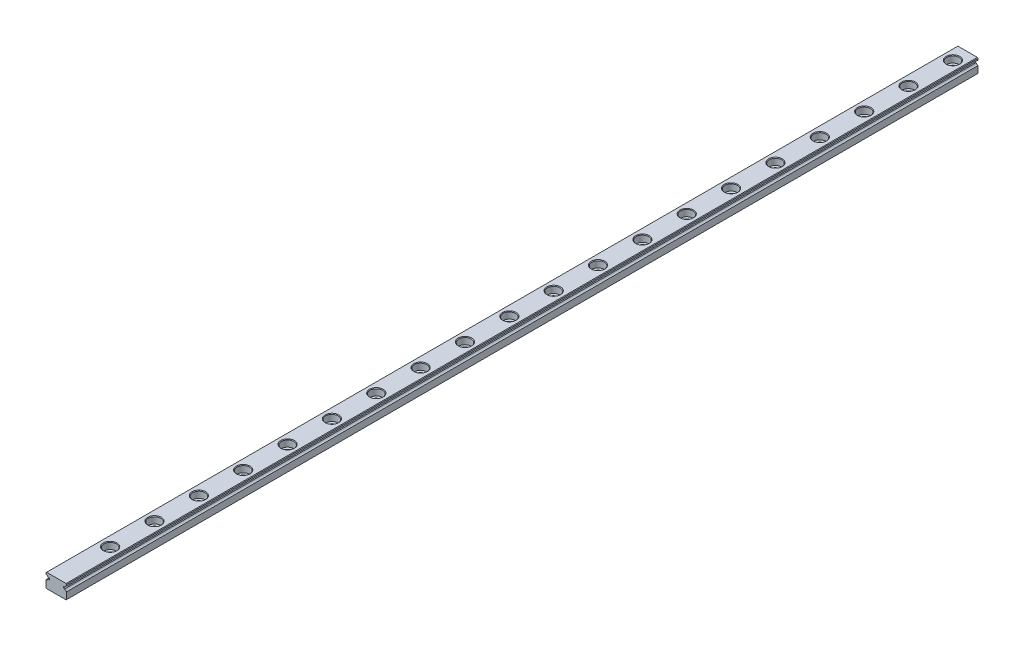
SolidWorks part; units mm, degrees
material "AISI 1020"
ref_plane "Спереди" through (0, 0, 0) normal (0, 0, 1) x (1, 0, 0)
ref_plane "Сверху" through (0, 0, 0) normal (0, 1, 0) x (1, 0, 0)
ref_plane "Справа" through (0, 0, 0) normal (1, 0, 0) x (0, 0, -1)
sketch "Sketch1" plane through (0, 0, 0) normal (0, 0, 1) x (1, 0, 0)
  line L0 (0, 0) -> (0, 4.3706) construction
  line L1 (-3.3, -2.4) -> (3.3, -2.4)
  line L2 (-3.5, -2.2) -> (-3.5, 0.1063)
  line L3 (-3.3, 2.4) -> (3.3, 2.4)
  line L4 (3.5, -2.2) -> (3.5, 0.1063)
  line L5 (-3.5, -2.4) -> (3.5, 2.4) construction
  line L6 (-3.5, 2.4) -> (3.5, -2.4) construction
  line L7 (-3.5, 1.6937) -> (-3.5, 2.2)
  line L8 (3.5, 1.6937) -> (3.5, 2.2)
  line L9 (-3.5, -2.2) -> (-3.3, -2.4)
  line L10 (3.3, -2.4) -> (3.5, -2.2)
  line L11 (3.3, 2.4) -> (3.5, 2.2)
  line L12 (-3.5, 2.2) -> (-3.3, 2.4)
  line L13 (2.8401, 0.65) -> (2.3401, 0.65)
  line L14 (-2.8401, 0.65) -> (-2.3401, 0.65)
  line L15 (2.3401, 0.65) -> (2.3401, 1.15)
  line L16 (-2.8401, 1.15) -> (-2.3401, 1.15)
  line L17 (-2.3401, 0.65) -> (-2.3401, 1.15)
  line L18 (2.8401, 1.15) -> (2.3401, 1.15)
  arc A0 (-3.5, 1.6937) -> (-2.8401, 1.15) centre (-3.6, 0.9) cw
  arc A1 (3.5, 1.6937) -> (2.8401, 1.15) centre (3.6, 0.9) ccw
  arc A2 (-2.8401, 0.65) -> (-3.5, 0.1063) centre (-3.6, 0.9) cw
  arc A3 (2.8401, 0.65) -> (3.5, 0.1063) centre (3.6, 0.9) ccw
  point P0 (0, 0)
  dimension "D4" = 0.8
  dimension "D5" = 0.1
  dimension "D1" = 7
  dimension "D2" = 4.8
  dimension "D3" = 1.5
  dimension "D6" = 0.5
  dimension "D7" = 0.5
extrude "Extrude1" add sketch "Sketch1" along normal offset from surface (308.2 mm away) 1
sketch "Sketch2" plane through (0, 2.4, 0) normal (0, 1, 0) x (1, 0, 0)
  line L0 (0, 0) -> (0, -5) construction
  circle A0 centre (0, -5) radius 1.2
  circle A1 centre (0, -5) radius 2.1
  dimension "D1" = 2.4
  dimension "D2" = 4.2
  dimension "D3" = 5
extrude "Extrude2" cut sketch "Sketch2" against normal up to next contours A0 region at (0, 2.4, 5)
extrude "Extrude4" cut sketch "Sketch" against normal blind 2.3
sketch "Sketch" plane through (0, 2.4, 0) normal (0, 1, 0) x (1, 0, 0) same geometry as "Sketch2"
chamfer "Chamfer1" distance 0.2 angle 45 2 edges at (0, -2.4, 6.2) (0, 2.4, 7.1)
pattern_linear "LPattern1" count 20 spacing 15 along (0, 0, 1) of "Extrude4", "Chamfer1", "Extrude2"
